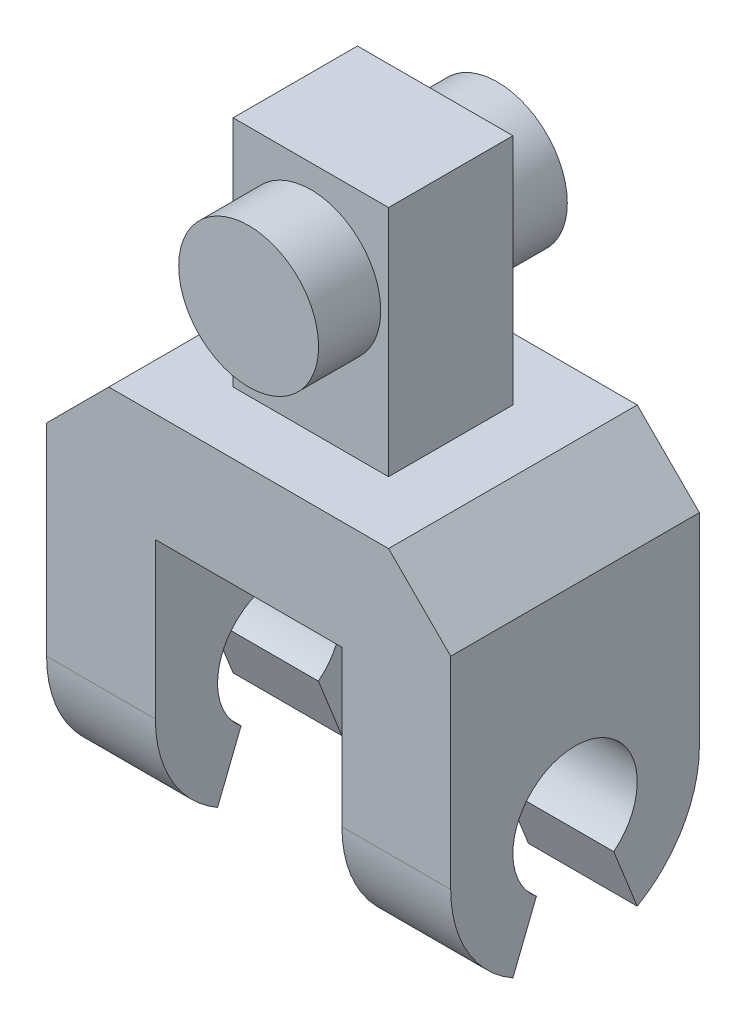
SolidWorks part; units mm, degrees
ref_plane "Front Plane" through (0, 0, 0) normal (0, 0, 1) x (1, 0, 0)
ref_plane "Top Plane" through (0, 0, 0) normal (0, 1, 0) x (1, 0, 0)
ref_plane "Right Plane" through (0, 0, 0) normal (1, 0, 0) x (0, 0, -1)
sketch "Sketch1" plane through (0, 0, 0) normal (1, 0, 0) x (0, 0, -1)
  line L0 (-8, 0) -> (-8, 10)
  line L1 (-8, 10) -> (8, 10)
  line L2 (8, 10) -> (8, 0)
  circle A0 centre (0, 0) radius 4
  arc A1 (-8, 0) -> (8, 0) centre (0, 0) ccw
  dimension "D1" = 8
  dimension "D2" = 10
  dimension "D3" = 16
extrude "Boss-Extrude1" add sketch "Sketch1" along normal blind 7 from offset 6
extrude "Boss-Extrude2" add sketch "Sketch1<2>" against normal blind 7 from offset 6 separate body offset against normal yes
sketch "Sketch1<2>" plane through (0, 0, 0) normal (1, 0, 0) x (0, 0, -1) same geometry as "Sketch1"
sketch "Sketch2" plane through (0, 10, 0) normal (0, 1, 0) x (1, 0, 0)
  line L1 (13, 8) -> (-13, 8)
  line L2 (13, 8) -> (13, -8)
  line L3 (13, -8) -> (-13, -8)
  line L4 (-13, 8) -> (-13, -8)
  line L5 (13, 8) -> (-13, -8) construction
  line L6 (13, -8) -> (-13, 8) construction
  point P0 (0, 0)
extrude "Boss-Extrude3" add sketch "Sketch2" along normal blind 7
chamfer "Chamfer1" distance 4 angle 45 2 edges at (-13, 17, 0) (13, 17, 0)
sketch "Sketch3" plane through (0, 17, 0) normal (0, 1, 0) x (1, 0, 0)
  line L1 (-5, 4) -> (5, 4)
  line L2 (-5, 4) -> (-5, -4)
  line L3 (-5, -4) -> (5, -4)
  line L4 (5, 4) -> (5, -4)
  line L5 (-5, 4) -> (5, -4) construction
  line L6 (-5, -4) -> (5, 4) construction
  point P0 (0, 0)
  dimension "D1" = 10
  dimension "D2" = 8
extrude "Boss-Extrude4" add sketch "Sketch3" along normal blind 15
sketch "Sketch5" plane through (0, 0, 0) normal (0, 0, 1) x (1, 0, 0)
  line L0 (-9, 17) -> (9, 17) construction
  circle A0 centre (0, 26) radius 4.5
  dimension "D2" = 9
  dimension "D1" = 9
extrude "Boss-Extrude5" add sketch "Sketch5" along normal mid plane 16
sketch "Sketch6" plane through (-13, 0, 0) normal (-1, 0, 0) x (0, 0, 1)
  line L0 (-2.4884, -3.1318) -> (-4, -6.9282)
  line L1 (2.4884, -3.1318) -> (4, -6.9282)
  line L3 (8, 0) -> (8, 13)
  line L4 (8, 13) -> (-8, 13)
  line L5 (-8, 13) -> (-8, 0)
  circle A0 centre (0, 0) radius 4 construction
  arc A1 (-8, 0) -> (8, 0) centre (0, 0) ccw
  arc A2 (-4, -6.9282) -> (4, -6.9282) centre (0, 0) ccw
  arc A3 (-2.4884, -3.1318) -> (2.4884, -3.1318) centre (0, 0) ccw
  dimension "D1" = 0
extrude "Cut-Extrude1" cut sketch "Sketch6" against normal up to surface (26 mm away) up to face at (13, 4.5, 0)
